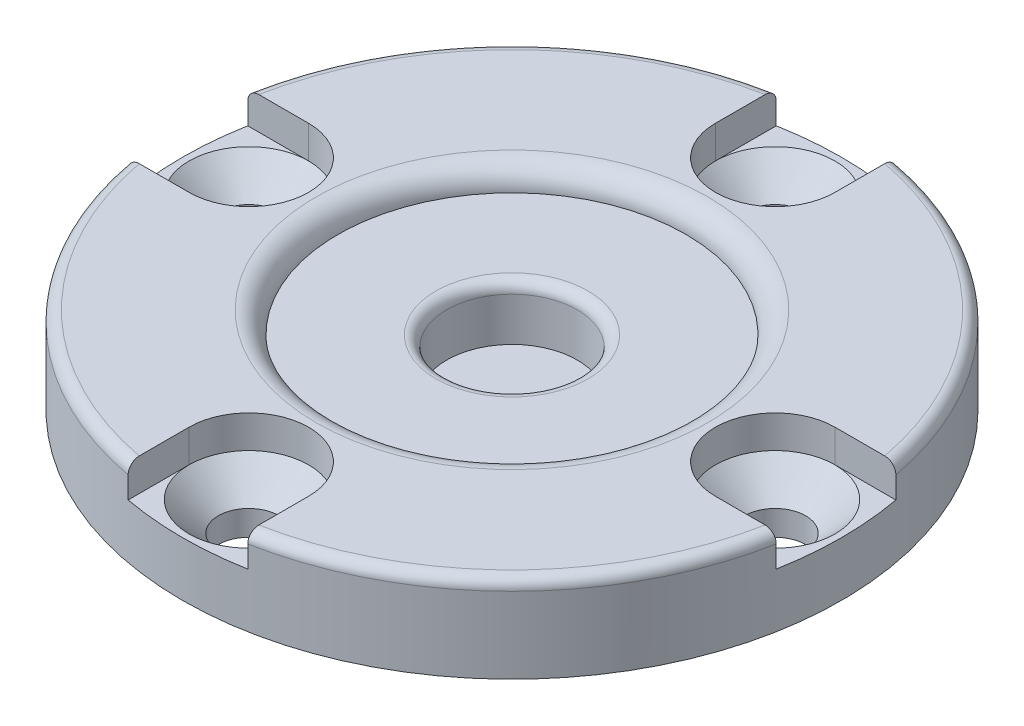
SolidWorks part; units mm, degrees
ref_plane "Front Plane" through (0, 0, 0) normal (0, 0, 1) x (1, 0, 0)
ref_plane "Top Plane" through (0, 0, 0) normal (0, 1, 0) x (1, 0, 0)
ref_plane "Right Plane" through (0, 0, 0) normal (1, 0, 0) x (0, 0, -1)
sketch "Sketch1" plane through (0, 0, 0) normal (0, 1, 0) x (1, 0, 0)
  circle A0 centre (0, 0) radius 15.15
  dimension "D1" = 30.3
extrude "Boss-Extrude1" add sketch "Sketch1" along normal blind 4
sketch "Sketch2" plane through (0, 4, 0) normal (0, 1, 0) x (1, 0, 0)
  line L0 (-2.75, 12.1) -> (-2.75, 14.8983)
  line L1 (2.75, 12.1) -> (2.75, 14.8983)
  line L2 (12.1, -2.75) -> (14.8983, -2.75)
  line L3 (12.1, 2.75) -> (14.8983, 2.75)
  line L4 (-2.75, -12.1) -> (-2.75, -14.8983)
  line L5 (2.75, -12.1) -> (2.75, -14.8983)
  line L6 (-12.1, 2.75) -> (-14.8983, 2.75)
  line L7 (-12.1, -2.75) -> (-14.8983, -2.75)
  circle A0 centre (0, 0) radius 12.1 construction
  arc A1 (-2.75, 12.1) -> (2.75, 12.1) centre (0, 12.1) ccw
  circle A2 centre (0, 0) radius 15.15 construction
  arc A3 (-2.75, 14.8983) -> (2.75, 14.8983) centre (0, 0) cw
  arc A4 (12.1, 2.75) -> (12.1, -2.75) centre (12.1, 0) ccw
  arc A5 (14.8983, 2.75) -> (14.8983, -2.75) centre (0, 0) cw
  arc A6 (2.75, -12.1) -> (-2.75, -12.1) centre (0, -12.1) ccw
  arc A7 (2.75, -14.8983) -> (-2.75, -14.8983) centre (0, 0) cw
  arc A8 (-12.1, -2.75) -> (-12.1, 2.75) centre (-12.1, 0) ccw
  arc A9 (-14.8983, -2.75) -> (-14.8983, 2.75) centre (0, 0) cw
  point P29 (0, 0)
  circle M18 centre (0, 0) radius 15.15
  dimension "D1" = 24.2
  dimension "D2" = 5.5
  dimension "D3" = 4
extrude "Cut-Extrude1" [suppressed] cut sketch "Sketch2" against normal blind 0.55
sketch "Sketch3" [suppressed] plane through (0, 1.45, 0) normal (0, 1, 0) x (1, 0, 0)
  circle A0 centre (0, 12.1) radius 1.4
  circle A1 centre (-12.1, 0) radius 1.4
  circle A2 centre (0, -12.1) radius 1.4
  circle A3 centre (12.1, 0) radius 1.4
  dimension "D1" = 2.8
extrude "Cut-Extrude2" [suppressed] cut sketch "Sketch3" against normal blind 2.55
sketch "Sketch4" plane through (0, 4, 0) normal (0, 1, 0) x (1, 0, 0)
  circle A0 centre (0, 0) radius 8
  dimension "D1" = 16
extrude "Cut-Extrude3" cut sketch "Sketch4" against normal blind 1
sketch "Sketch5" plane through (0, 3, 0) normal (0, 1, 0) x (1, 0, 0)
  circle A0 centre (0, 0) radius 3
  dimension "D1" = 6
extrude "Cut-Extrude4" cut sketch "Sketch5" against normal blind 2.5
fillet "Fillet1" radius 1 1 edges at (0, 4, 8)
fillet "Fillet2" radius 0.5 1 edges at (0, 3, 3)
fillet "Fillet3" radius 0.5 1 edges at (0, 4, 15.15)
extrude "Cut-Extrude5" cut sketch "Sketch2<2>" against normal blind 1.5 contours L7 A8 L6 M18 | L5 A6 L4 M18 | L3 A4 L2 M18 | A1 L1 A3 L0 region at (-12.4671, 4, 0) region at (12.4671, 4, 0) region at (0, 4, 12.4671)
sketch "Sketch2<2>" plane through (0, 4, 0) normal (0, 1, 0) x (1, 0, 0) same geometry as "Sketch2"
hole_wizard "CSK for M2.5 Flat Head Machine Screw1" positions "Sketch6" profile "Sketch7" countersink size "M2.5" standard "ANSI Metric" end condition through all
sketch "Sketch6" plane through (0, 2.5, 0) normal (0, 1, 0) x (1, 0, 0)
  point P0 (0, 12.1)
  point P3 (-12.1, 0)
  point P6 (12.1, 0)
  point P9 (0, -12.1)
sketch "Sketch7" plane through (0, 2.5, -12.1) normal (1, 0, 0) x (0, 0, 1)
  line L0 (0, 0) -> (0, 2.5)
  line L1 (0, 2.5) -> (1.4, 2.5)
  line L2 (1.4, 2.5) -> (1.4, 1.35)
  line L3 (1.4, 1.35) -> (2.75, 0)
  line L5 (2.75, 0) -> (0, 0)
  line L6 (-1.4, 1.35) -> (-2.75, 0) construction
  line L11 (0, -6.35) -> (0, 107.95) construction
  dimension "Thru Hole Dia." = 2.8
  dimension "Thru Hole Depth" = 2.5
  dimension "Near C'Sink Dia." = 5.5
  dimension "Near C'Sink Angle" = 90
